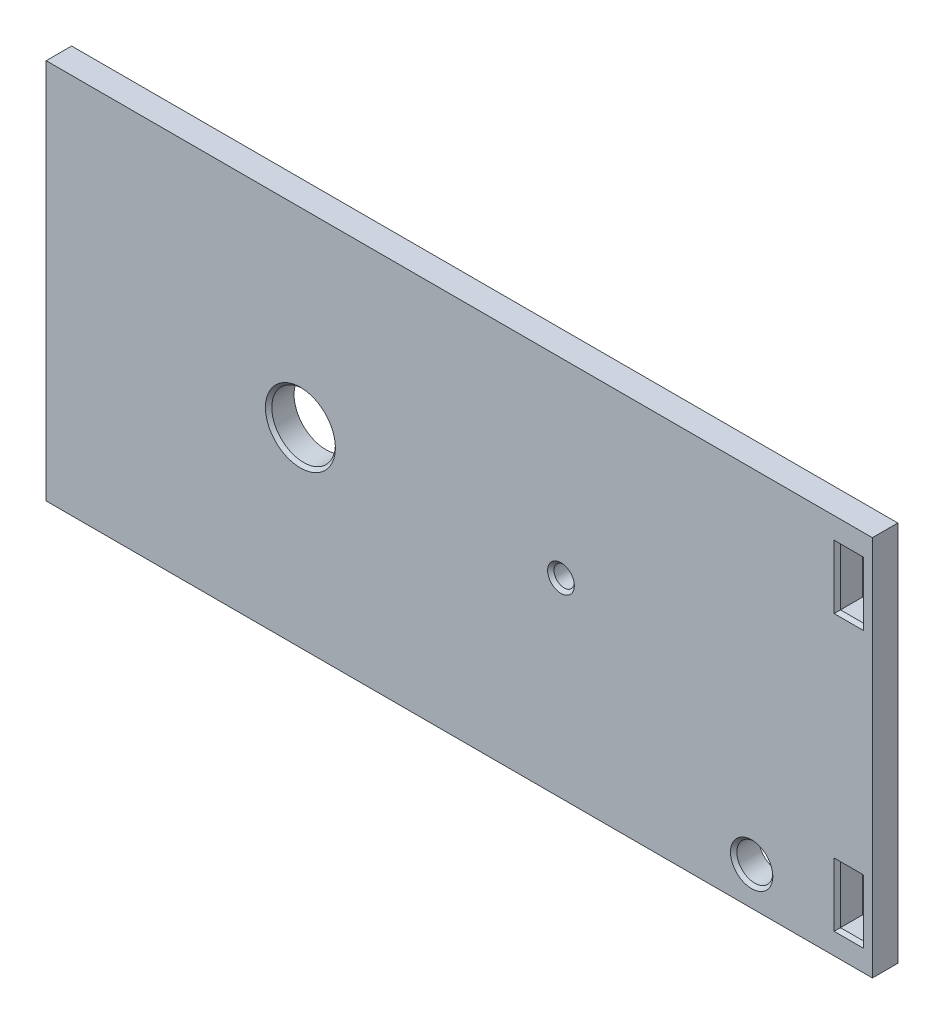
SolidWorks part; units mm, degrees
ref_plane "Front Plane" through (0, 0, 0) normal (0, 0, 1) x (1, 0, 0)
ref_plane "Top Plane" through (0, 0, 0) normal (0, 1, 0) x (1, 0, 0)
ref_plane "Right Plane" through (0, 0, 0) normal (1, 0, 0) x (0, 0, -1)
sketch "Sketch1" plane through (0, 0, 0) normal (0, 0, 1) x (1, 0, 0)
  line L2 (-65, -30) -> (-65, 30)
  line L12 (61.3, 26.15) -> (61.3, 17.15) construction
  line L13 (-65, 30) -> (65, 30)
  line L15 (-65, -30) -> (65, -30)
  line L16 (65, 30) -> (65, -30)
  line L17 (59.475, 26.15) -> (63.125, 26.15)
  line L18 (59.475, 26.15) -> (59.475, 17.15)
  line L19 (59.475, 17.15) -> (63.125, 17.15)
  line L20 (63.125, 26.15) -> (63.125, 17.15)
  line L21 (59.475, -17.15) -> (63.125, -17.15)
  line L22 (59.475, -17.15) -> (59.475, -26.15)
  line L23 (59.475, -26.15) -> (63.125, -26.15)
  line L24 (63.125, -17.15) -> (63.125, -26.15)
  line L25 (61.3, -17.15) -> (61.3, -26.15) construction
  line L26 (63.125, 21.65) -> (59.475, 21.65) construction
  line L27 (63.125, -21.65) -> (59.475, -21.65) construction
  circle A3 centre (-25, 0) radius 5
  circle A4 centre (46, -24) radius 2.83
  circle A6 centre (16, 0) radius 1.6
  point P2 (0, 30)
  point P9 (65, 0)
  dimension "D6" = 10
  dimension "D4" = 5.66
  dimension "D2" = 60
  dimension "D3" = 130
  dimension "D8" = 24
  dimension "D1" = 9
  dimension "D9" = 3.65
  dimension "D10" = 21.65
  dimension "D11" = 21.65
  dimension "D5" = 40
  dimension "D7" = 86.3
  dimension "D12" = 71
  dimension "D13" = 41
extrude "Boss-Extrude1" add sketch "Sketch1" along normal mid plane 4
chamfer "Chamfer1" distance 0.5 angle 45 11 edges at (61.3, 17.15, 2) (59.475, 21.65, 2) (61.3, 26.15, 2) (63.125, 21.65, 2) (-20, 0, 2) (48.83, -24, 2) (61.3, -26.15, 2) (59.475, -21.65, 2) (61.3, -17.15, 2) (63.125, -21.65, 2) (17.6, 0, 2)
sketch "Sketch3" plane through (0, 0, -2) normal (0, 0, -1) x (-1, 0, 0)
  line L0 (-61.3, 26.15) -> (-61.3, 17.15) construction
  line L1 (-63.125, 21.65) -> (-59.475, 21.65) construction
  line L2 (-61.3, -17.15) -> (-61.3, -26.15) construction
  line L3 (-59.475, -17.15) -> (-63.125, -17.15) construction
  line L4 (-63.125, -21.65) -> (-59.475, -21.65) construction
equation "\"hole_width\"=3.4"
equation "\"hole_length\"=8.7"
equation "\"pin_hole_height\"=9"
equation "\"D1@Sketch1\"=\"pin_hole_height\""
equation "\"pin_hole_width\"=3.65"
equation "\"D9@Sketch1\"=\"pin_hole_width\""
equation "\"wall_thick_ness\"=4"
equation "\"D1@Boss-Extrude1\"=\"wall_thick_ness\""
equation "\"back_boost\"= 7"
equation "\"D5@Sketch1\"=\"back_boost\"+33.00mm"
equation "\"D3@Sketch1\"=123.00mm+\"back_boost\""
